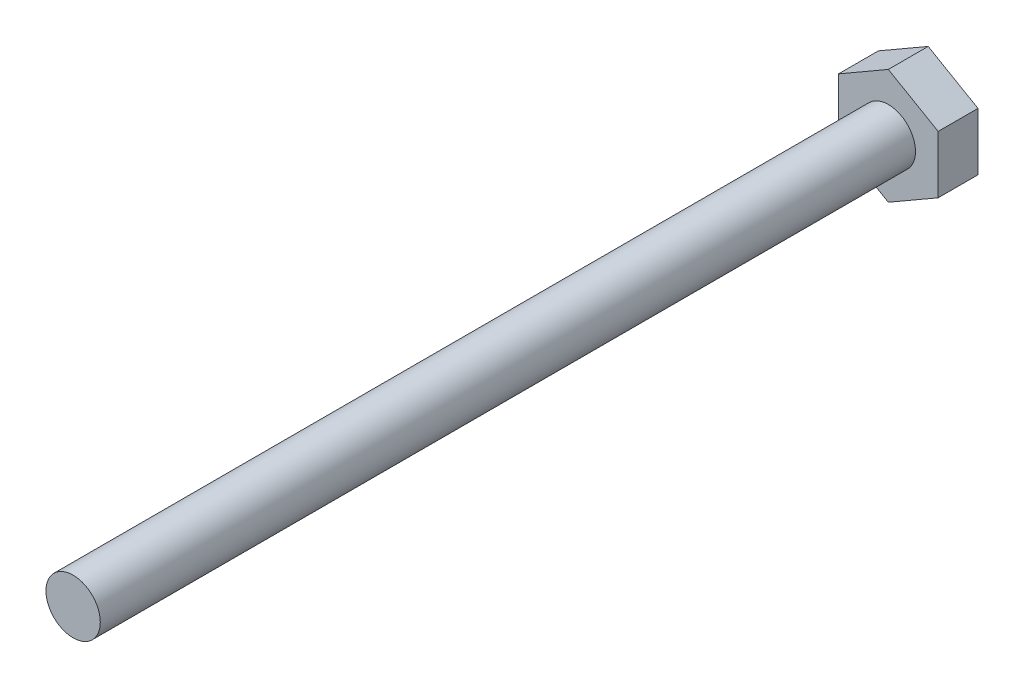
SolidWorks part; units mm, degrees
ref_plane "前视基准面" through (0, 0, 0) normal (0, 0, 1) x (1, 0, 0)
ref_plane "上视基准面" through (0, 0, 0) normal (0, 1, 0) x (1, 0, 0)
ref_plane "右视基准面" through (0, 0, 0) normal (1, 0, 0) x (0, 0, -1)
sketch "草图1" plane through (0, 0, 0) normal (0, 0, 1) x (1, 0, 0)
  line L0 (0, -2.75) -> (0, -3.1754) construction
  line L1 (0, -3.1754) -> (2.75, -1.5877)
  line L2 (2.75, -1.5877) -> (2.75, 1.5877)
  line L3 (2.75, 1.5877) -> (0, 3.1754)
  line L4 (0, 3.1754) -> (-2.75, 1.5877)
  line L5 (-2.75, 1.5877) -> (-2.75, -1.5877)
  line L6 (-2.75, -1.5877) -> (0, -3.1754)
  line L8 (0.249, 0.9029) -> (-0.249, 0.9029)
  line L9 (-0.249, 0.9029) -> (-0.249, 0.249)
  line L10 (-0.249, 0.249) -> (-0.9029, 0.249)
  line L11 (-0.9029, 0.249) -> (-0.9029, -0.249)
  line L12 (0.9029, 0.249) -> (0.9029, -0.249)
  line L13 (0.249, 0.249) -> (0.9029, 0.249)
  line L14 (0.249, 0.9029) -> (0.249, 0.249)
  line L15 (0.249, -0.249) -> (0.9029, -0.249)
  line L16 (0.249, -0.9029) -> (0.249, -0.249)
  line L17 (0.249, -0.9029) -> (-0.249, -0.9029)
  line L18 (-0.249, -0.9029) -> (-0.249, -0.249)
  line L19 (-0.249, -0.249) -> (-0.9029, -0.249)
  circle A0 centre (0, 0) radius 2.75 construction
  circle A1 centre (0, 0) radius 1.5
  point P1 (2.75, 0)
  point P23 (0, 0.9029)
  point P24 (0.9029, 0)
  point P29 (-0.9029, 0)
  dimension "D1" = 5.5
extrude "凸台-拉伸3" add sketch "草图1" along normal blind 2.2 contours L5 L6 L1 L2 L3 L4 A1 region at (-1.333, -2.3088, 0)
extrude "凸台-拉伸4" add sketch "草图1<6>" along normal blind 47.2 contours A1 L18 L19 L11 L10 L9 L8 L14 L13 L12 L15 L16 L17 | L19 L18 L17 L16 L15 L12 L13 L14 L8 L9 L10 L11 region at (0, 0, 0) region at (-1.4576, 0, 0)
sketch "草图1<6>" plane through (0, 0, 0) normal (0, 0, 1) x (1, 0, 0) same geometry as "草图1"
extrude "切除-拉伸1" cut sketch "草图1<9>" against normal blind 1 and the other way blind 1 contours L19 L18 L17 L16 L15 L12 L13 L14 L8 L9 L10 L11 region at (0, 0, 0)
sketch "草图1<9>" plane through (0, 0, 0) normal (0, 0, 1) x (1, 0, 0) same geometry as "草图1"
